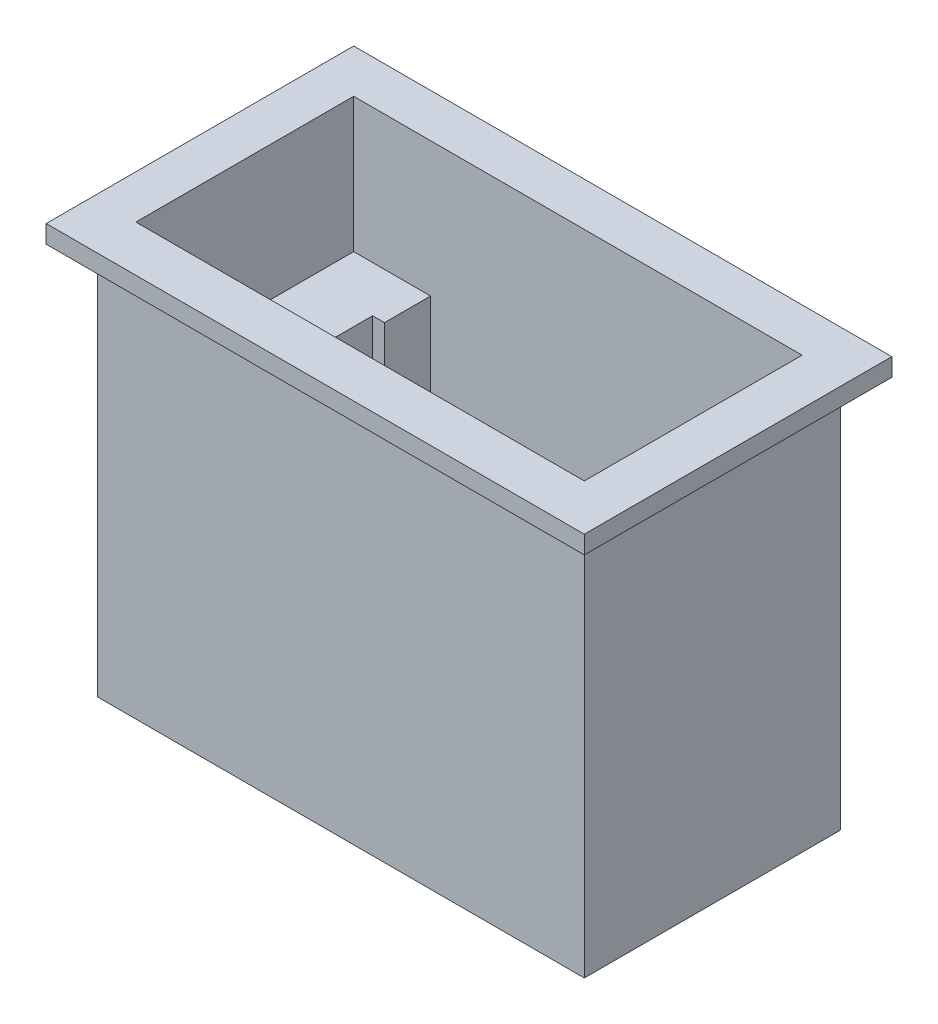
SolidWorks part; units mm, degrees
ref_plane "Front Plane" through (0, 0, 0) normal (0, 0, 1) x (1, 0, 0)
ref_plane "Top Plane" through (0, 0, 0) normal (0, 1, 0) x (1, 0, 0)
ref_plane "Right Plane" through (0, 0, 0) normal (1, 0, 0) x (0, 0, -1)
sketch "Sketch1" plane through (0, 0, 0) normal (0, 1, 0) x (1, 0, 0)
  line L1 (-10.4, 5.9429) -> (27.6, 5.9429)
  line L2 (-10.4, 5.9429) -> (-10.4, -14.0571)
  line L3 (-10.4, -14.0571) -> (27.6, -14.0571)
  line L4 (27.6, 5.9429) -> (27.6, -14.0571)
  dimension "D1" = 38
  dimension "D2" = 20
extrude "Boss-Extrude1" add sketch "Sketch1" along normal blind 32
sketch "Sketch2" plane through (0, 32, 0) normal (0, 1, 0) x (1, 0, 0)
  line L0 (27.6, 5.9429) -> (-10.4, 5.9429) construction
  line L1 (-9, 4.5429) -> (26, 4.5429)
  line L2 (-9, 4.5429) -> (-9, -12.4571)
  line L3 (-9, -12.4571) -> (26, -12.4571)
  line L4 (26, 4.5429) -> (26, -12.4571)
  line L5 (-10.4, 5.9429) -> (-10.4, -14.0571) construction
  dimension "D1" = 35
  dimension "D2" = 17
  dimension "D3" = 1.4
  dimension "D4" = 1.4
extrude "Cut-Extrude1" cut sketch "Sketch2" against normal blind 28
sketch "Sketch3" plane through (0, 4, 0) normal (0, 1, 0) x (1, 0, 0)
  line L0 (-9, -12.4571) -> (26, -12.4571) construction
  line L1 (-9, 4.5429) -> (-3, 4.5429)
  line L2 (-9, 4.5429) -> (-9, -12.4571)
  line L3 (-9, -12.4571) -> (-3, -12.4571)
  line L4 (-3, 4.5429) -> (-3, -12.4571)
  line L5 (26, 4.5429) -> (-9, 4.5429) construction
  line L6 (20, 4.5429) -> (26, 4.5429)
  line L7 (20, 4.5429) -> (20, -12.4571)
  line L8 (20, -12.4571) -> (26, -12.4571)
  line L9 (26, 4.5429) -> (26, -12.4571)
  dimension "D1" = 6
  dimension "D2" = 6
extrude "Boss-Extrude2" add sketch "Sketch3" along normal blind 17.5
sketch "Sketch4" plane through (0, 32, 0) normal (0, 1, 0) x (1, 0, 0)
  line L1 (-10.4, 5.9429) -> (27.6, 5.9429)
  line L2 (-10.4, 5.9429) -> (-10.4, -14.0571)
  line L3 (-10.4, -14.0571) -> (27.6, -14.0571)
  line L4 (27.6, 5.9429) -> (27.6, -14.0571)
extrude "Extrude-Thin2" add sketch "Sketch4" against normal blind 1.4 thin thin type one direction wall 2
sketch "Sketch5" plane through (0, 21.5, 0) normal (0, 1, 0) x (1, 0, 0)
  line L0 (-3, -12.4571) -> (-3, 4.5429) construction
  circle A0 centre (-5.5, -3.8921) radius 1
  point P4 (-7, -3.8921)
  dimension "D1" = 2
  dimension "D2" = 2.5
extrude "Cut-Extrude2" cut sketch "Sketch5" against normal blind 3
sketch "Sketch6" plane through (0, 21.5, 0) normal (0, 1, 0) x (1, 0, 0)
  circle A0 centre (22.9531, -4.1157) radius 1
  point P4 (22.9531, -4.1157)
  dimension "D1" = 2
extrude "Cut-Extrude3" cut sketch "Sketch6" against normal blind 3
sketch "Sketch7" plane through (0, 21.5, 0) normal (0, 1, 0) x (1, 0, 0)
  line L1 (-3.9278, -7.0563) -> (-1.4278, -7.0563)
  line L2 (-3.9278, -7.0563) -> (-3.9278, 0.9437)
  line L3 (-3.9278, 0.9437) -> (-1.4278, 0.9437)
  line L4 (-1.4278, -7.0563) -> (-1.4278, 0.9437)
  dimension "D1" = 8
  dimension "D2" = 2.5
extrude "Cut-Extrude4" cut sketch "Sketch7" against normal through all
